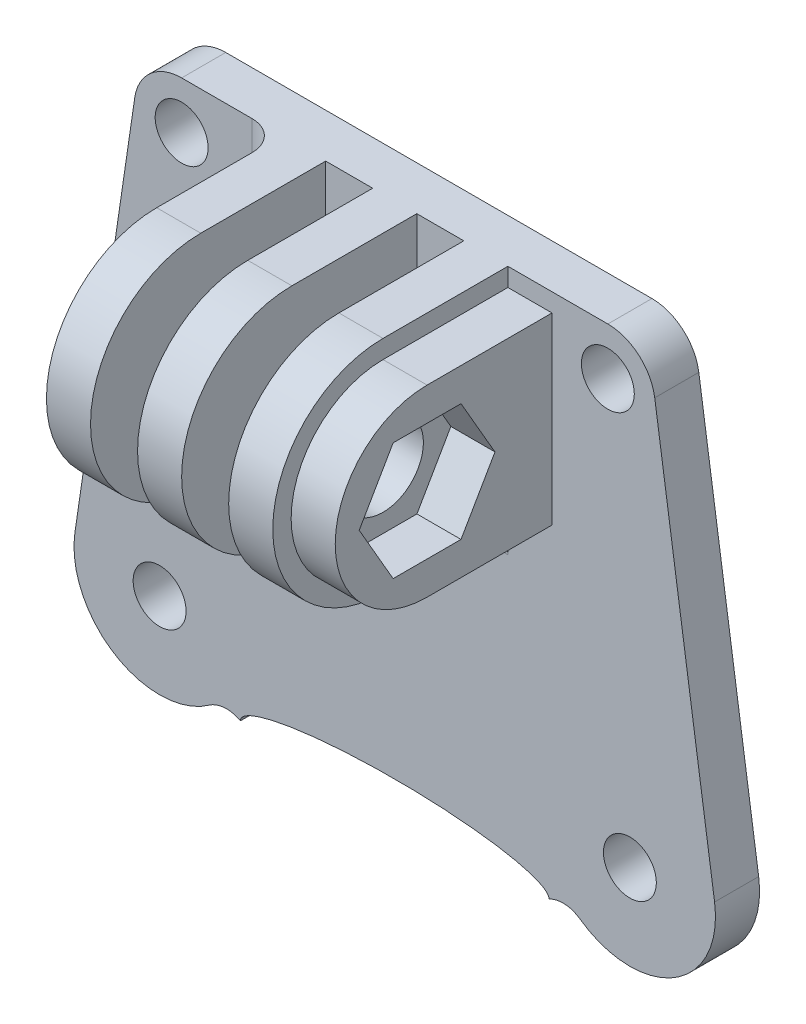
SolidWorks part; units mm, degrees
ref_plane "Front Plane" through (0, 0, 0) normal (0, 0, 1) x (1, 0, 0)
ref_plane "Top Plane" through (0, 0, 0) normal (0, 1, 0) x (1, 0, 0)
ref_plane "Right Plane" through (0, 0, 0) normal (1, 0, 0) x (0, 0, -1)
sketch "Sketch1" plane through (0, 0, 0) normal (0, 0, 1) x (1, 0, 0)
  line L3 (-17.6906, -52.4767) -> (-21.7629, -80.152)
  line L4 (21.7629, -80.152) -> (17.6906, -52.4767)
  line L5 (14.5, -49.7212) -> (-14.5, -49.7212)
  line L6 (-17.6906, -52.4767) -> (-21.7629, -80.152)
  line L7 (21.7629, -80.152) -> (17.6906, -52.4767)
  line L8 (14.5, -49.7212) -> (-14.5, -49.7212)
  circle A0 centre (14.5, -52.9462) radius 1.8 construction
  circle A1 centre (14.5, -52.9462) radius 1.8
  circle A2 centre (-14.5, -52.9462) radius 1.8 construction
  circle A3 centre (-14.5, -52.9462) radius 1.8
  circle A4 centre (16, -81) radius 1.8 construction
  circle A5 centre (16, -81) radius 1.8
  arc A6 (-21.7629, -80.152) -> (-12.6145, -85.7402) centre (-16, -81) ccw
  arc A7 (-10.5, -85.6089) -> (-12.6145, -85.7402) centre (-11.4521, -87.3677) ccw
  arc A8 (12.6145, -85.7402) -> (10.5, -85.6089) centre (11.4521, -87.3677) ccw
  arc A9 (12.6145, -85.7402) -> (21.7629, -80.152) centre (16, -81) ccw
  arc A10 (17.6906, -52.4767) -> (14.5, -49.7212) centre (14.5, -52.9462) ccw
  arc A11 (-14.5, -49.7212) -> (-17.6906, -52.4767) centre (-14.5, -52.9462) ccw
  arc A12 (-21.7629, -80.152) -> (-12.6145, -85.7402) centre (-16, -81) ccw
  arc A13 (-10.5, -85.6089) -> (-12.6145, -85.7402) centre (-11.4521, -87.3677) ccw
  arc A14 (12.6145, -85.7402) -> (10.5, -85.6089) centre (11.4521, -87.3677) ccw
  arc A15 (12.6145, -85.7402) -> (21.7629, -80.152) centre (16, -81) ccw
  arc A16 (17.6906, -52.4767) -> (14.5, -49.7212) centre (14.5, -52.9462) ccw
  arc A17 (-14.5, -49.7212) -> (-17.6906, -52.4767) centre (-14.5, -52.9462) ccw
  circle A18 centre (-16, -81) radius 1.8 construction
  circle A19 centre (-16, -81) radius 1.8
  ellipse E1 centre (0, -85.6089) end of major axis (-10.5, -85.6089) minor radius 1.8233 (10.5, -85.6089) -> (-10.5, -85.6089) ccw
  ellipse E2 centre (0, -85.6089) end of major axis (-10.5, -85.6089) minor radius 1.8233 (10.5, -85.6089) -> (-10.5, -85.6089) ccw
  dimension "D1" = 0
extrude "Boss-Extrude1" add sketch "Sketch1" along normal blind 3
sketch "Sketch2" plane through (0, 0, 3) normal (0, 0, 1) x (1, 0, 0)
  line L0 (0, -49.7212) -> (0, -83.7856) construction
  line L1 (14.5, -49.7212) -> (-14.5, -49.7212) construction
  line L2 (-18.3888, -57.2212) -> (18.3888, -57.2212) construction
  line L3 (-1.5, -49.7212) -> (1.5, -49.7212)
  line L4 (-1.5, -49.7212) -> (-1.5, -64.7212)
  line L5 (-1.5, -64.7212) -> (1.5, -64.7212)
  line L6 (1.5, -49.7212) -> (1.5, -64.7212)
  line L7 (-1.5, -49.7212) -> (1.5, -64.7212) construction
  line L8 (-1.5, -64.7212) -> (1.5, -49.7212) construction
  line L9 (-17.6906, -52.4767) -> (-21.7629, -80.152) construction
  line L10 (21.7629, -80.152) -> (17.6906, -52.4767) construction
  line L12 (-7.7, -49.7212) -> (-4.7, -49.7212)
  line L13 (-7.7, -49.7212) -> (-7.7, -64.7212)
  line L14 (-7.7, -64.7212) -> (-4.7, -64.7212)
  line L15 (-4.7, -49.7212) -> (-4.7, -64.7212)
  line L16 (-7.7, -49.7212) -> (-4.7, -64.7212) construction
  line L17 (-7.7, -64.7212) -> (-4.7, -49.7212) construction
  line L18 (4.7, -49.7212) -> (7.7, -49.7212)
  line L19 (4.7, -49.7212) -> (4.7, -64.7212)
  line L20 (4.7, -64.7212) -> (7.7, -64.7212)
  line L21 (7.7, -49.7212) -> (7.7, -64.7212)
  line L22 (4.7, -49.7212) -> (7.7, -64.7212) construction
  line L23 (4.7, -64.7212) -> (7.7, -49.7212) construction
  ellipse E0 centre (0, -85.6089) end of major axis (-10.5, -85.6089) minor radius 1.8233 (10.5, -85.6089) -> (-10.5, -85.6089) ccw construction
  point P12 (0, -57.2212)
  point P23 (-6.2, -57.2212)
  point P28 (6.2, -57.2212)
  dimension "D1" = 3
  dimension "D2" = 15
  dimension "D3" = 3
  dimension "D4" = 3
  dimension "D5" = 3.2
  dimension "D6" = 3.2
extrude "Boss-Extrude2" add sketch "Sketch2" along normal blind 16
sketch "Sketch3" plane through (7.7, 0, 0) normal (1, 0, 0) x (0, 0, -1)
  line L0 (-19, -57.2212) -> (-3, -57.2212) construction
  line L1 (-19, -64.7212) -> (-19, -49.7212) construction
  line L2 (-3, -64.7212) -> (-3, -49.7212) construction
  line L4 (-19, -64.7212) -> (-3, -64.7212) construction
  line L5 (-11.5, -49.7212) -> (-19, -49.7212)
  line L6 (-19, -49.7212) -> (-19, -64.7212)
  line L7 (-19, -64.7212) -> (-11.5, -64.7212)
  circle A0 centre (-11.5, -57.2212) radius 7.5
  circle A1 centre (-11.5, -57.2212) radius 2.75
  line M2 (-3, -49.7212) -> (-19, -49.7212)
  line M3 (-19, -49.7212) -> (-19, -64.7212)
  line M4 (-19, -64.7212) -> (-3, -64.7212)
  dimension "D1" = 5.5
extrude "Cut-Extrude1" cut sketch "Sketch3" against normal up to surface (15.4 mm away) contours A0 L6 M4 | A0 M2 M3 | L0 A1 | A1 L0 region at (7.7, -58.3883, 11.5) region at (7.7, -56.054, 11.5) region at (7.7, -51.3964, 17.3247) region at (7.7, -63.0459, 17.3247) up to face at (-7.7, -57.2212, 11)
sketch "Sketch4" plane through (7.7, 0, 0) normal (1, 0, 0) x (0, 0, -1)
  line L0 (-11.5, -57.2212) -> (-3, -57.2212) construction
  line L1 (-6.8812, -57.2212) -> (-9.1906, -53.2212)
  line L2 (-9.1906, -53.2212) -> (-13.8094, -53.2212)
  line L3 (-13.8094, -53.2212) -> (-16.1188, -57.2212)
  line L4 (-16.1188, -57.2212) -> (-13.8094, -61.2212)
  line L5 (-13.8094, -61.2212) -> (-9.1906, -61.2212)
  line L6 (-9.1906, -61.2212) -> (-6.8812, -57.2212)
  line L7 (-3, -64.7212) -> (-3, -49.7212) construction
  line L8 (-11.5, -50.9712) -> (-3, -50.9712)
  line L9 (-11.5, -63.4712) -> (-3, -63.4712)
  line L10 (-3, -63.4712) -> (-3, -50.9712)
  circle A0 centre (-11.5, -57.2212) radius 4 construction
  circle A1 centre (-11.5, -57.2212) radius 6.25
  line M5 (-3, -64.7212) -> (-3, -49.7212)
  dimension "D2" = 12.5
  dimension "D1" = 8
extrude "Boss-Extrude3" add sketch "Sketch4" along normal blind 3 contours A1 L6 L5 L4 L3 L2 L1 | A1 L9 L8 M5 region at (7.7, -57.2212, 5.0666) region at (7.7, -52.9267, 7.2056)
fillet "Fillet1" radius 2 4 edges at (-7.7, -57.2212, 3) (6.2, -64.7212, 3) (0, -64.7212, 3) (-6.2, -64.7212, 3)
